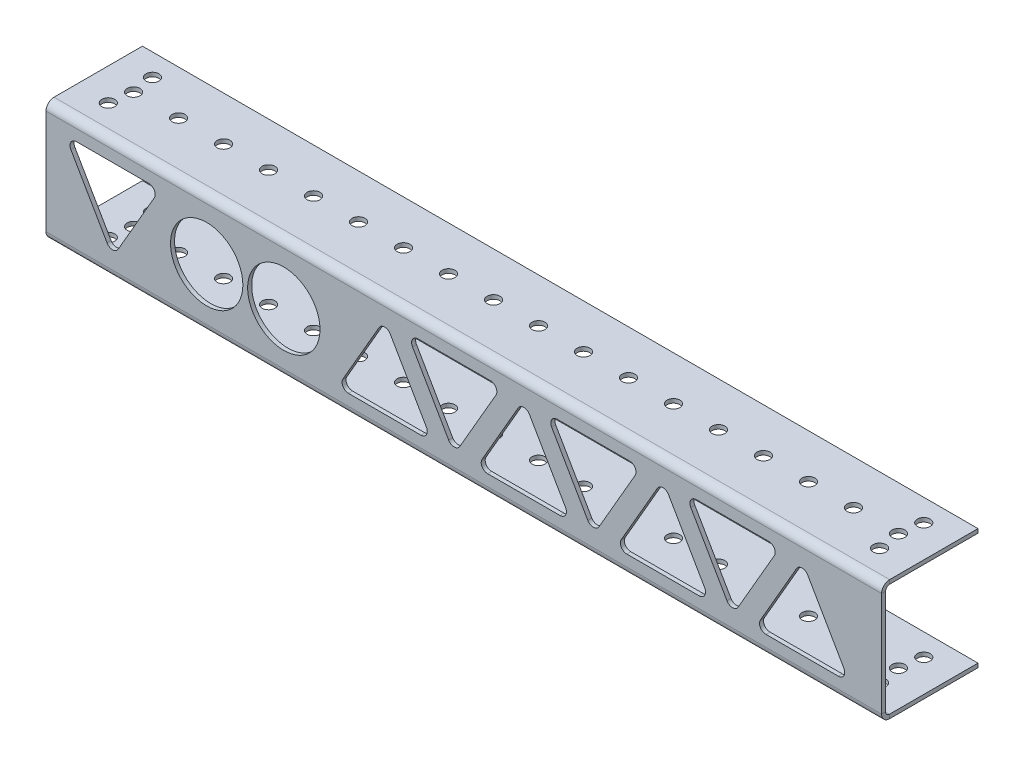
SolidWorks part; units mm, degrees
note: The reader was unsure of these and kept them because the rebuilt part matched: bend radius of "Base-Flange1", "BaseBend1", "BaseBend2".
ref_plane "Front Plane" through (0, 0, 0) normal (0, 0, 1) x (1, 0, 0)
ref_plane "Top Plane" through (0, 0, 0) normal (0, 1, 0) x (1, 0, 0)
ref_plane "Right Plane" through (0, 0, 0) normal (1, 0, 0) x (0, 0, -1)
sketch "Sketch1" plane through (0, 0, 0) normal (1, 0, 0) x (0, 0, -1)
  line L0 (18.2562, 22.225) -> (-18.2563, 22.225)
  line L1 (-18.2563, 22.225) -> (-18.2563, -22.225)
  line L2 (-18.2563, -22.225) -> (18.2562, -22.225)
  line L3 (0, 22.225) -> (0, -22.225) construction
  line L4 (0, 0) -> (-18.2563, 0) construction
  point P10 (0, 0)
  dimension "D1" = 44.45
  dimension "D2" = 36.5125
base flange "Base-Flange1" sketch "Sketch1" end condition mid plane depth 330.2 reverse direction no thickness 1.5875 reverse thickness direction no bend radius 1.5875
bend "BaseBend1" bend radius 1.5875 bend angle 90 parameters "D5"=1
bend "BaseBend2" bend radius 1.5875 bend angle 90 parameters "D5"=2
sketch "Sketch6" plane through (0, 23.8125, 0) normal (0, 1, 0) x (1, 0, 0)
  line L0 (165.1, 0.7937) -> (-165.1, 0.7937) construction
  line L1 (165.1, 18.2562) -> (165.1, -16.6688) construction
  line L2 (-165.1, 18.2562) -> (-165.1, -16.6688) construction
  line L3 (151.13, 0.7937) -> (165.1, -16.6688) construction
  line L4 (-151.13, 0.7937) -> (-165.1, -16.6688) construction
  circle A0 centre (151.13, 0.7937) radius 2.54
  circle A1 centre (133.35, 0.7937) radius 2.54
  circle A2 centre (115.57, 0.7937) radius 2.54
  circle A3 centre (97.79, 0.7937) radius 2.54
  circle A4 centre (80.01, 0.7937) radius 2.54
  circle A5 centre (62.23, 0.7937) radius 2.54
  circle A6 centre (44.45, 0.7937) radius 2.54
  circle A7 centre (26.67, 0.7937) radius 2.54
  circle A8 centre (8.89, 0.7937) radius 2.54
  circle A9 centre (-8.89, 0.7937) radius 2.54
  circle A10 centre (-26.67, 0.7937) radius 2.54
  circle A11 centre (-44.45, 0.7937) radius 2.54
  circle A12 centre (-62.23, 0.7937) radius 2.54
  circle A13 centre (-80.01, 0.7937) radius 2.54
  circle A14 centre (-97.79, 0.7937) radius 2.54
  circle A15 centre (-115.57, 0.7937) radius 2.54
  circle A16 centre (-133.35, 0.7937) radius 2.54
  circle A17 centre (-151.13, 0.7937) radius 2.54
  dimension "D1" = 18
  dimension "D2" = 5.08
  dimension "D3" = 17.78
extrude "Cut-Extrude1" cut sketch "Sketch6" against normal through all normal cut yes
sketch "Sketch8" plane through (0, 0, 19.8438) normal (0, 0, 1) x (1, 0, 0)
  line L0 (-165.1, 0) -> (165.1, 0) construction
  line L1 (-165.1, 20.6375) -> (-165.1, -20.6375) construction
  line L2 (165.1, 20.6375) -> (165.1, -20.6375) construction
  circle A0 centre (-101.6, 0) radius 14.2875
  dimension "D1" = 28.575
  dimension "D2" = 63.5
extrude "Cut-Extrude2" cut sketch "Sketch8" against normal through all normal cut yes
sketch "Sketch9" plane through (0, 0, 19.8438) normal (0, 0, 1) x (1, 0, 0)
  line L0 (135.9022, 12.3825) -> (150.2003, -12.3825)
  line L1 (148.0006, -16.1925) -> (119.4044, -16.1925)
  line L2 (117.2047, -12.3825) -> (131.5028, 12.3825)
  line L3 (165.1, 20.6375) -> (165.1, -20.6375) construction
  line L4 (165.1, 23.8125) -> (-165.1, 23.8125) construction
  line L5 (165.1, -23.8125) -> (-165.1, -23.8125) construction
  line L6 (91.9081, 16.1925) -> (120.5043, 16.1925)
  line L7 (122.704, 12.3825) -> (108.4059, -12.3825)
  line L8 (104.0065, -12.3825) -> (89.7084, 12.3825)
  line L9 (62.2121, -12.3825) -> (76.5102, 12.3825)
  line L10 (80.9096, 12.3825) -> (95.2077, -12.3825)
  line L11 (93.008, -16.1925) -> (64.4118, -16.1925)
  line L12 (34.7158, 12.3825) -> (49.0139, -12.3825)
  line L13 (53.4133, -12.3825) -> (67.7114, 12.3825)
  line L14 (65.5117, 16.1925) -> (36.9155, 16.1925)
  line L15 (21.5176, 12.3825) -> (7.2195, -12.3825)
  line L16 (9.4192, -16.1925) -> (38.0154, -16.1925)
  line L17 (40.2151, -12.3825) -> (25.917, 12.3825)
  line L18 (-18.0771, 16.1925) -> (10.5191, 16.1925)
  line L19 (12.7188, 12.3825) -> (-1.5793, -12.3825)
  line L20 (-5.9787, -12.3825) -> (-20.2768, 12.3825)
  line L21 (-33.475, 12.3825) -> (-47.7731, -12.3825)
  line L22 (-45.5734, -16.1925) -> (-16.9772, -16.1925)
  line L23 (-14.7775, -12.3825) -> (-29.0756, 12.3825)
  arc A0 (150.2003, -12.3825) -> (148.0006, -16.1925) centre (148.0006, -13.6525) cw
  arc A1 (119.4044, -16.1925) -> (117.2047, -12.3825) centre (119.4044, -13.6525) cw
  arc A2 (135.9022, 12.3825) -> (131.5028, 12.3825) centre (133.7025, 11.1125) ccw
  arc A3 (120.5043, 16.1925) -> (122.704, 12.3825) centre (120.5043, 13.6525) cw
  arc A4 (91.9081, 16.1925) -> (89.7084, 12.3825) centre (91.9081, 13.6525) ccw
  arc A5 (108.4059, -12.3825) -> (104.0065, -12.3825) centre (106.2062, -11.1125) cw
  arc A6 (95.2077, -12.3825) -> (93.008, -16.1925) centre (93.008, -13.6525) cw
  arc A7 (62.2121, -12.3825) -> (64.4118, -16.1925) centre (64.4118, -13.6525) ccw
  arc A8 (76.5102, 12.3825) -> (80.9096, 12.3825) centre (78.7099, 11.1125) cw
  arc A9 (67.7114, 12.3825) -> (65.5117, 16.1925) centre (65.5117, 13.6525) ccw
  arc A10 (34.7158, 12.3825) -> (36.9155, 16.1925) centre (36.9155, 13.6525) cw
  arc A11 (49.0139, -12.3825) -> (53.4133, -12.3825) centre (51.2136, -11.1125) ccw
  arc A12 (38.0154, -16.1925) -> (40.2151, -12.3825) centre (38.0154, -13.6525) ccw
  arc A13 (7.2195, -12.3825) -> (9.4192, -16.1925) centre (9.4192, -13.6525) ccw
  arc A14 (21.5176, 12.3825) -> (25.917, 12.3825) centre (23.7173, 11.1125) cw
  arc A15 (10.5191, 16.1925) -> (12.7188, 12.3825) centre (10.5191, 13.6525) cw
  arc A16 (-18.0771, 16.1925) -> (-20.2768, 12.3825) centre (-18.0771, 13.6525) ccw
  arc A17 (-1.5793, -12.3825) -> (-5.9787, -12.3825) centre (-3.779, -11.1125) cw
  arc A18 (-16.9772, -16.1925) -> (-14.7775, -12.3825) centre (-16.9772, -13.6525) ccw
  arc A19 (-47.7731, -12.3825) -> (-45.5734, -16.1925) centre (-45.5734, -13.6525) ccw
  arc A20 (-33.475, 12.3825) -> (-29.0756, 12.3825) centre (-31.2753, 11.1125) cw
  circle A21 centre (-101.6, 0) radius 15.24 construction
  circle A22 centre (-71.12, 0) radius 15.24 construction
  circle A23 centre (-71.12, 0) radius 14.2875
  point P32 (152.4, -16.1925)
  point P37 (133.7025, 16.1925)
  point P44 (106.2062, -16.1925)
  point P51 (78.7099, 16.1925)
  point P56 (32.5161, 16.1925)
  point P59 (51.2136, -16.1925)
  point P66 (23.7173, 16.1925)
  point P73 (-3.779, -16.1925)
  point P80 (-31.2753, 16.1925)
  dimension "D13" = 2.54
  dimension "D12" = 30.48
  dimension "D14" = 28.575
  dimension "D1" = 12.7
  dimension "D2" = 60
  dimension "D3" = 60
  dimension "D4" = 7.62
  dimension "D5" = 7.62
  dimension "D6" = 7.62
  dimension "D7" = 7.62
  dimension "D8" = 7.62
  dimension "D9" = 7.62
  dimension "D10" = 7.62
  dimension "D11" = 7.62
extrude "Cut-Extrude3" cut sketch "Sketch9" against normal blind 2.54
sketch "Sketch10" plane through (0, 0, 19.8438) normal (0, 0, 1) x (1, 0, 0)
  line L0 (-155.2803, 12.3825) -> (-140.9822, -12.3825)
  line L1 (-136.5828, -12.3825) -> (-122.2847, 12.3825)
  line L2 (-124.4844, 16.1925) -> (-153.0806, 16.1925)
  line L3 (10.5191, 16.1925) -> (-18.0771, 16.1925) construction
  line L4 (-45.5734, -16.1925) -> (-16.9772, -16.1925) construction
  line L5 (-14.7775, -12.3825) -> (-29.0756, 12.3825) construction
  line L6 (-1.5793, -12.3825) -> (12.7188, 12.3825) construction
  line L7 (-165.1, 20.6375) -> (-165.1, -20.6375) construction
  arc A0 (-140.9822, -12.3825) -> (-136.5828, -12.3825) centre (-138.7825, -11.1125) ccw
  arc A1 (-122.2847, 12.3825) -> (-124.4844, 16.1925) centre (-124.4844, 13.6525) ccw
  arc A2 (-155.2803, 12.3825) -> (-153.0806, 16.1925) centre (-153.0806, 13.6525) cw
  point P15 (-138.7825, -16.1925)
  point P20 (-157.48, 16.1925)
  dimension "D2" = 2.54
  dimension "D1" = 7.62
extrude "Cut-Extrude4" cut sketch "Sketch10" against normal blind 2.54
sketch "Sketch11" plane through (0, 23.8125, 0) normal (0, 1, 0) x (1, 0, 0)
  line L0 (-152.4, 18.2562) -> (-152.4, -16.6688) construction
  line L1 (165.1, 18.2562) -> (-165.1, 18.2562) construction
  line L2 (165.1, -16.6688) -> (-165.1, -16.6688) construction
  line L3 (-165.1, 18.2562) -> (-152.4, 9.525) construction
  line L4 (-152.4, 9.525) -> (-165.1, 0.7937) construction
  line L5 (-165.1, 18.2562) -> (-165.1, -16.6688) construction
  line L6 (-165.1, 0.7937) -> (-152.4, -7.9375) construction
  line L7 (-152.4, -7.9375) -> (-165.1, -16.6688) construction
  line L8 (0, 0) -> (0, -16.6688) construction
  circle A0 centre (-152.4, 9.525) radius 2.54
  circle A1 centre (-152.4, -7.9375) radius 2.54
  circle A2 centre (152.4, -7.9375) radius 2.54
  circle A3 centre (152.4, 9.525) radius 2.54
  circle A4 centre (152.4, -7.9375) radius 2.54
  circle A5 centre (152.4, 9.525) radius 2.54
  dimension "D2" = 5.08
  dimension "D1" = 12.7
extrude "Cut-Extrude5" cut sketch "Sketch11" against normal through all contours A3 | A2 | A1 | A0 normal cut yes
sketch "Bend-Lines1" [suppressed] plane through (0, 0, 0) normal (0, 1, 0) x (1, 0, 0)
sketch "Bounding-Box1" [suppressed] plane through (0, 0, 0) normal (0, 1, 0) x (1, 0, 0)
sheet metal parameters "Sheet-Metal2" thickness 1.5875 parameters "D1"=1.5875
flat pattern "Flat-Pattern2" [suppressed]
sketch "Bend-Lines2" plane through (0, 0, 18.2563) normal (0, 0, -1) x (-1, 0, 0)
  line L0 (-165.1, 22.5077) -> (165.1, 22.5077) construction
  line L1 (165.1, -22.5077) -> (-165.1, -22.5077) construction
  line L2 (-165.1, 22.5077) -> (165.1, 22.5077) construction
  line L3 (165.1, -22.5077) -> (-165.1, -22.5077) construction
sketch3d "Bounding-Box2" [suppressed]
  line L0 (330.2, -81.528, 0) -> (0, -81.528, 0) construction
  line L1 (330.2, 37.078, 0) -> (0, 37.078, 0) construction
  line L2 (330.2, -81.528, 0) -> (330.2, 37.078, 0) construction
  line L3 (0, -81.528, 0) -> (0, 37.078, 0) construction
bend of the flat pattern "Flatten-<BaseBend1>1"
bend of the flat pattern "Flatten-<BaseBend2>1"
sketch "Sketch6-1" [suppressed] plane through (0, 41.0467, 19.8438) normal (0, 0, 1) x (1, 0, 0)
  line L0 (165.1, 0.7937) -> (-165.1, 0.7937) construction
sheet metal parameters "Sheet-Metal3" thickness 1.5875 parameters "D1"=1.5875
flat pattern "Flat-Pattern2" [suppressed]
sketch "Bend-Lines2" plane through (0, 0, 18.2563) normal (0, 0, -1) x (-1, 0, 0)
  line L0 (-165.1, 22.5077) -> (165.1, 22.5077) construction
  line L1 (165.1, -22.5077) -> (-165.1, -22.5077) construction
  line L2 (-165.1, 22.5077) -> (165.1, 22.5077) construction
  line L3 (165.1, -22.5077) -> (-165.1, -22.5077) construction
sketch3d "Bounding-Box2" [suppressed]
  line L0 (330.2, -81.528, 0) -> (0, -81.528, 0) construction
  line L1 (330.2, 37.078, 0) -> (0, 37.078, 0) construction
  line L2 (330.2, -81.528, 0) -> (330.2, 37.078, 0) construction
  line L3 (0, -81.528, 0) -> (0, 37.078, 0) construction
bend of the flat pattern "Flatten-<BaseBend1>1"
bend of the flat pattern "Flatten-<BaseBend2>1"
sketch "Sketch6-1" [suppressed] plane through (0, 41.0467, 19.8438) normal (0, 0, 1) x (1, 0, 0)
  line L0 (165.1, 0.7937) -> (-165.1, 0.7937) construction
  line L3 (151.13, 0.7937) -> (165.1, -16.6688) construction
  line L4 (-151.13, 0.7937) -> (-165.1, -16.6688) construction
  circle A0 centre (151.13, 0.7937) radius 2.54
  circle A1 centre (133.35, 0.7937) radius 2.54
  circle A2 centre (115.57, 0.7937) radius 2.54
  circle A3 centre (97.79, 0.7937) radius 2.54
  circle A4 centre (80.01, 0.7937) radius 2.54
  circle A5 centre (62.23, 0.7937) radius 2.54
  circle A6 centre (44.45, 0.7937) radius 2.54
  circle A7 centre (26.67, 0.7937) radius 2.54
  circle A8 centre (8.89, 0.7937) radius 2.54
  circle A9 centre (-8.89, 0.7937) radius 2.54
  circle A10 centre (-26.67, 0.7937) radius 2.54
  circle A11 centre (-44.45, 0.7937) radius 2.54
  circle A12 centre (-62.23, 0.7937) radius 2.54
  circle A13 centre (-80.01, 0.7937) radius 2.54
  circle A14 centre (-97.79, 0.7937) radius 2.54
  circle A15 centre (-115.57, 0.7937) radius 2.54
  circle A16 centre (-133.35, 0.7937) radius 2.54
  circle A17 centre (-151.13, 0.7937) radius 2.54
  dimension "D1" = 18
  dimension "D2" = 5.08
  dimension "D3" = 17.78
sheet metal parameters "Sheet-Metal4" thickness 1.5875 parameters "D1"=1.5875
flat pattern "Flat-Pattern2" [suppressed]
sketch "Bend-Lines2" plane through (0, 0, 18.2563) normal (0, 0, -1) x (-1, 0, 0)
  line L0 (-165.1, 22.5077) -> (165.1, 22.5077) construction
  line L1 (165.1, -22.5077) -> (-165.1, -22.5077) construction
  line L2 (-165.1, 22.5077) -> (165.1, 22.5077) construction
  line L3 (165.1, -22.5077) -> (-165.1, -22.5077) construction
sketch3d "Bounding-Box2" [suppressed]
  line L0 (330.2, -81.528, 0) -> (0, -81.528, 0) construction
  line L1 (330.2, 37.078, 0) -> (0, 37.078, 0) construction
  line L2 (330.2, -81.528, 0) -> (330.2, 37.078, 0) construction
  line L3 (0, -81.528, 0) -> (0, 37.078, 0) construction
bend of the flat pattern "Flatten-<BaseBend1>1"
bend of the flat pattern "Flatten-<BaseBend2>1"
sketch "Sketch6-1" [suppressed] plane through (0, 41.0467, 19.8438) normal (0, 0, 1) x (1, 0, 0)
  line L0 (165.1, 0.7937) -> (-165.1, 0.7937) construction
  line L3 (151.13, 0.7937) -> (165.1, -16.6688) construction
  line L4 (-151.13, 0.7937) -> (-165.1, -16.6688) construction
  circle A0 centre (151.13, 0.7937) radius 2.54
  circle A1 centre (133.35, 0.7937) radius 2.54
  circle A2 centre (115.57, 0.7937) radius 2.54
  circle A3 centre (97.79, 0.7937) radius 2.54
  circle A4 centre (80.01, 0.7937) radius 2.54
  circle A5 centre (62.23, 0.7937) radius 2.54
  circle A6 centre (44.45, 0.7937) radius 2.54
  circle A7 centre (26.67, 0.7937) radius 2.54
  circle A8 centre (8.89, 0.7937) radius 2.54
  circle A9 centre (-8.89, 0.7937) radius 2.54
  circle A10 centre (-26.67, 0.7937) radius 2.54
  circle A11 centre (-44.45, 0.7937) radius 2.54
  circle A12 centre (-62.23, 0.7937) radius 2.54
  circle A13 centre (-80.01, 0.7937) radius 2.54
  circle A14 centre (-97.79, 0.7937) radius 2.54
  circle A15 centre (-115.57, 0.7937) radius 2.54
  circle A16 centre (-133.35, 0.7937) radius 2.54
  circle A17 centre (-151.13, 0.7937) radius 2.54
  dimension "D1" = 18
  dimension "D2" = 5.08
  dimension "D3" = 17.78
sheet metal parameters "Sheet-Metal5" thickness 1.5875 parameters "D1"=1.5875
flat pattern "Flat-Pattern2" [suppressed]
sketch "Bend-Lines2" plane through (0, 0, 18.2563) normal (0, 0, -1) x (-1, 0, 0)
  line L0 (-165.1, 22.5077) -> (165.1, 22.5077) construction
  line L1 (165.1, -22.5077) -> (-165.1, -22.5077) construction
  line L2 (-165.1, 22.5077) -> (165.1, 22.5077) construction
  line L3 (165.1, -22.5077) -> (-165.1, -22.5077) construction
sketch3d "Bounding-Box2" [suppressed]
  line L0 (330.2, -81.528, 0) -> (0, -81.528, 0) construction
  line L1 (330.2, 37.078, 0) -> (0, 37.078, 0) construction
  line L2 (330.2, -81.528, 0) -> (330.2, 37.078, 0) construction
  line L3 (0, -81.528, 0) -> (0, 37.078, 0) construction
bend of the flat pattern "Flatten-<BaseBend1>1"
bend of the flat pattern "Flatten-<BaseBend2>1"
sketch "Sketch6-1" [suppressed] plane through (0, 41.0467, 19.8438) normal (0, 0, 1) x (1, 0, 0)
  line L0 (165.1, 0.7937) -> (-165.1, 0.7937) construction
  line L3 (151.13, 0.7937) -> (165.1, -16.6688) construction
  line L4 (-151.13, 0.7937) -> (-165.1, -16.6688) construction
  circle A0 centre (151.13, 0.7937) radius 2.54
  circle A1 centre (133.35, 0.7937) radius 2.54
  circle A2 centre (115.57, 0.7937) radius 2.54
  circle A3 centre (97.79, 0.7937) radius 2.54
  circle A4 centre (80.01, 0.7937) radius 2.54
  circle A5 centre (62.23, 0.7937) radius 2.54
  circle A6 centre (44.45, 0.7937) radius 2.54
  circle A7 centre (26.67, 0.7937) radius 2.54
  circle A8 centre (8.89, 0.7937) radius 2.54
  circle A9 centre (-8.89, 0.7937) radius 2.54
  circle A10 centre (-26.67, 0.7937) radius 2.54
  circle A11 centre (-44.45, 0.7937) radius 2.54
  circle A12 centre (-62.23, 0.7937) radius 2.54
  circle A13 centre (-80.01, 0.7937) radius 2.54
  circle A14 centre (-97.79, 0.7937) radius 2.54
  circle A15 centre (-115.57, 0.7937) radius 2.54
  circle A16 centre (-133.35, 0.7937) radius 2.54
  circle A17 centre (-151.13, 0.7937) radius 2.54
  dimension "D1" = 18
  dimension "D2" = 5.08
  dimension "D3" = 17.78
sheet metal parameters "Sheet-Metal6" thickness 1.5875 parameters "D1"=1.5875
flat pattern "Flat-Pattern2" [suppressed]
sketch "Bend-Lines2" plane through (0, 0, 18.2563) normal (0, 0, -1) x (-1, 0, 0)
  line L0 (-165.1, 22.5077) -> (165.1, 22.5077) construction
  line L1 (165.1, -22.5077) -> (-165.1, -22.5077) construction
  line L2 (-165.1, 22.5077) -> (165.1, 22.5077) construction
  line L3 (165.1, -22.5077) -> (-165.1, -22.5077) construction
sketch3d "Bounding-Box2" [suppressed]
  line L0 (330.2, -81.528, 0) -> (0, -81.528, 0) construction
  line L1 (330.2, 37.078, 0) -> (0, 37.078, 0) construction
  line L2 (330.2, -81.528, 0) -> (330.2, 37.078, 0) construction
  line L3 (0, -81.528, 0) -> (0, 37.078, 0) construction
bend of the flat pattern "Flatten-<BaseBend1>1"
bend of the flat pattern "Flatten-<BaseBend2>1"
sketch "Sketch6-1" [suppressed] plane through (0, 41.0467, 19.8438) normal (0, 0, 1) x (1, 0, 0)
  line L0 (165.1, 0.7937) -> (-165.1, 0.7937) construction
  line L3 (151.13, 0.7937) -> (165.1, -16.6688) construction
  line L4 (-151.13, 0.7937) -> (-165.1, -16.6688) construction
  circle A0 centre (151.13, 0.7937) radius 2.54
  circle A1 centre (133.35, 0.7937) radius 2.54
  circle A2 centre (115.57, 0.7937) radius 2.54
  circle A3 centre (97.79, 0.7937) radius 2.54
  circle A4 centre (80.01, 0.7937) radius 2.54
  circle A5 centre (62.23, 0.7937) radius 2.54
  circle A6 centre (44.45, 0.7937) radius 2.54
  circle A7 centre (26.67, 0.7937) radius 2.54
  circle A8 centre (8.89, 0.7937) radius 2.54
  circle A9 centre (-8.89, 0.7937) radius 2.54
  circle A10 centre (-26.67, 0.7937) radius 2.54
  circle A11 centre (-44.45, 0.7937) radius 2.54
  circle A12 centre (-62.23, 0.7937) radius 2.54
  circle A13 centre (-80.01, 0.7937) radius 2.54
  circle A14 centre (-97.79, 0.7937) radius 2.54
  circle A15 centre (-115.57, 0.7937) radius 2.54
  circle A16 centre (-133.35, 0.7937) radius 2.54
  circle A17 centre (-151.13, 0.7937) radius 2.54
  dimension "D1" = 18
  dimension "D2" = 5.08
  dimension "D3" = 17.78
sheet metal parameters "Sheet-Metal7" thickness 1.5875 parameters "D1"=1.5875
flat pattern "Flat-Pattern2" [suppressed]
sketch "Bend-Lines2" plane through (0, 0, 18.2563) normal (0, 0, -1) x (-1, 0, 0)
  line L0 (-165.1, 22.5077) -> (165.1, 22.5077) construction
  line L1 (165.1, -22.5077) -> (-165.1, -22.5077) construction
  line L2 (-165.1, 22.5077) -> (165.1, 22.5077) construction
  line L3 (165.1, -22.5077) -> (-165.1, -22.5077) construction
sketch3d "Bounding-Box2" [suppressed]
  line L0 (330.2, -81.528, 0) -> (0, -81.528, 0) construction
  line L1 (330.2, 37.078, 0) -> (0, 37.078, 0) construction
  line L2 (330.2, -81.528, 0) -> (330.2, 37.078, 0) construction
  line L3 (0, -81.528, 0) -> (0, 37.078, 0) construction
bend of the flat pattern "Flatten-<BaseBend1>1"
bend of the flat pattern "Flatten-<BaseBend2>1"
sketch "Sketch6-1" [suppressed] plane through (0, 41.0467, 19.8438) normal (0, 0, 1) x (1, 0, 0)
  line L0 (165.1, 0.7937) -> (-165.1, 0.7937) construction
  line L3 (151.13, 0.7937) -> (165.1, -16.6688) construction
  line L4 (-151.13, 0.7937) -> (-165.1, -16.6688) construction
  circle A0 centre (151.13, 0.7937) radius 2.54
  circle A1 centre (133.35, 0.7937) radius 2.54
  circle A2 centre (115.57, 0.7937) radius 2.54
  circle A3 centre (97.79, 0.7937) radius 2.54
  circle A4 centre (80.01, 0.7937) radius 2.54
  circle A5 centre (62.23, 0.7937) radius 2.54
  circle A6 centre (44.45, 0.7937) radius 2.54
  circle A7 centre (26.67, 0.7937) radius 2.54
  circle A8 centre (8.89, 0.7937) radius 2.54
  circle A9 centre (-8.89, 0.7937) radius 2.54
  circle A10 centre (-26.67, 0.7937) radius 2.54
  circle A11 centre (-44.45, 0.7937) radius 2.54
  circle A12 centre (-62.23, 0.7937) radius 2.54
  circle A13 centre (-80.01, 0.7937) radius 2.54
  circle A14 centre (-97.79, 0.7937) radius 2.54
  circle A15 centre (-115.57, 0.7937) radius 2.54
  circle A16 centre (-133.35, 0.7937) radius 2.54
  circle A17 centre (-151.13, 0.7937) radius 2.54
  dimension "D1" = 18
  dimension "D2" = 5.08
  dimension "D3" = 17.78
